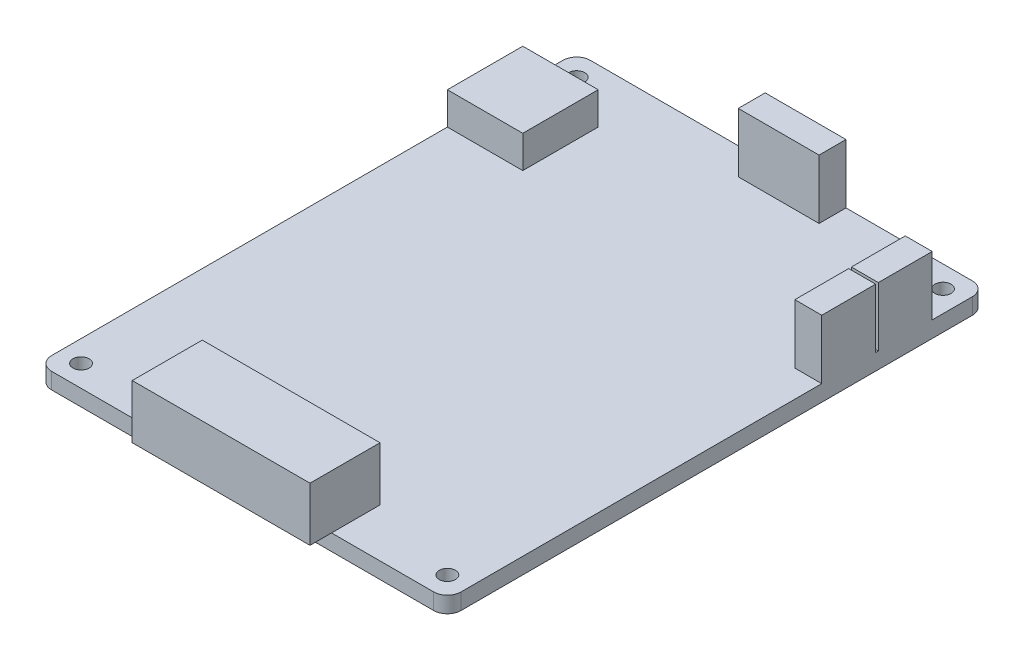
SolidWorks part; units mm, degrees
ref_plane "Front Plane" through (0, 0, 0) normal (0, 0, 1) x (1, 0, 0)
ref_plane "Top Plane" through (0, 0, 0) normal (0, 1, 0) x (1, 0, 0)
ref_plane "Right Plane" through (0, 0, 0) normal (1, 0, 0) x (0, 0, -1)
sketch "Sketch1" plane through (0, 0, 0) normal (0, 1, 0) x (1, 0, 0)
  line L1 (-38, -50) -> (38, -50)
  line L2 (-38, -50) -> (-38, 50)
  line L3 (-38, 50) -> (38, 50)
  line L4 (38, -50) -> (38, 50)
  line L5 (-38, -50) -> (38, 50) construction
  line L6 (-38, 50) -> (38, -50) construction
  point P0 (0, 0)
  dimension "D1" = 76
  dimension "D2" = 100
extrude "Boss-Extrude1" add sketch "Sketch1" along normal mid plane 3
fillet "Fillet1" radius 2.54 4 edges at (-38, 0, -50) (38, 0, -50) (-38, 0, 50) (38, 0, 50)
sketch "Sketch2" plane through (0, 1.5, 0) normal (0, 1, 0) x (1, 0, 0)
  line L0 (38, -47.46) -> (38, 47.46) construction
  line L1 (-34, -46) -> (34, -46) construction
  line L2 (-34, -46) -> (-34, 46) construction
  line L3 (-34, 46) -> (34, 46) construction
  line L4 (34, -46) -> (34, 46) construction
  line L5 (-34, -46) -> (34, 46) construction
  line L6 (-34, 46) -> (34, -46) construction
  line L7 (35.46, 50) -> (-35.46, 50) construction
  circle A0 centre (-34, 46) radius 1.5
  circle A1 centre (34, 46) radius 1.5
  circle A2 centre (34, -46) radius 1.5
  circle A3 centre (-34, -46) radius 1.5
  point P0 (0, 0)
  dimension "D3" = 3
  dimension "D1" = 4
  dimension "D2" = 4
extrude "Cut-Extrude1" cut sketch "Sketch2" against normal through all
sketch "Sketch3" plane through (0, 1.5, 0) normal (0, 1, 0) x (1, 0, 0)
  line L0 (-35.46, -50) -> (35.46, -50) construction
  line L1 (16.5, -54) -> (-16.5, -54)
  line L2 (16.5, -54) -> (16.5, -41)
  line L3 (16.5, -41) -> (-16.5, -41)
  line L4 (-16.5, -54) -> (-16.5, -41)
  line L5 (16.5, -54) -> (-16.5, -41) construction
  line L6 (16.5, -41) -> (-16.5, -54) construction
  point P0 (0, -47.5)
  point P5 (0, 0)
  dimension "D1" = 33
  dimension "D2" = 13
  dimension "D3" = 4
extrude "Boss-Extrude2" add sketch "Sketch3" along normal blind 10
sketch "Sketch4" plane through (0, 1.5, 0) normal (0, 1, 0) x (1, 0, 0)
  line L0 (35.46, 50) -> (-35.46, 50) construction
  line L1 (-24, 26) -> (-38, 26)
  line L2 (-24, 26) -> (-24, 40)
  line L3 (-24, 40) -> (-38, 40)
  line L4 (-38, 26) -> (-38, 40)
  line L5 (-24, 26) -> (-38, 40) construction
  line L6 (-24, 40) -> (-38, 26) construction
  line L8 (-38, 47.46) -> (-38, -47.46) construction
  point P0 (-31, 33)
  dimension "D1" = 10
  dimension "D2" = 14
  dimension "D3" = 14
extrude "Boss-Extrude3" add sketch "Sketch4" along normal blind 6
sketch "Sketch5" plane through (0, 1.5, 0) normal (0, 1, 0) x (1, 0, 0)
  line L0 (38, -47.46) -> (38, 47.46) construction
  line L1 (12, 45) -> (-3, 45)
  line L2 (12, 45) -> (12, 50)
  line L3 (12, 50) -> (-3, 50)
  line L4 (-3, 45) -> (-3, 50)
  line L5 (12, 45) -> (-3, 50) construction
  line L6 (12, 50) -> (-3, 45) construction
  line L7 (33, 30) -> (38, 30)
  line L8 (33, 30) -> (33, 40)
  line L9 (33, 40) -> (38, 40)
  line L10 (38, 30) -> (38, 40)
  line L11 (33, 30) -> (38, 40) construction
  line L12 (33, 40) -> (38, 30) construction
  line L13 (33, 19.5) -> (38, 19.5)
  line L14 (33, 19.5) -> (33, 29.5)
  line L15 (33, 29.5) -> (38, 29.5)
  line L16 (38, 19.5) -> (38, 29.5)
  line L17 (33, 19.5) -> (38, 29.5) construction
  line L18 (33, 29.5) -> (38, 19.5) construction
  line L19 (35.46, 50) -> (-35.46, 50) construction
  point P0 (4.5, 47.5)
  point P5 (35.5, 35)
  point P10 (35.5, 24.5)
  dimension "D1" = 10
  dimension "D2" = 10
  dimension "D3" = 0.5
  dimension "D4" = 10
  dimension "D5" = 5
  dimension "D6" = 15
  dimension "D7" = 26
  dimension "D8" = 5
extrude "Boss-Extrude4" add sketch "Sketch5" along normal blind 11
